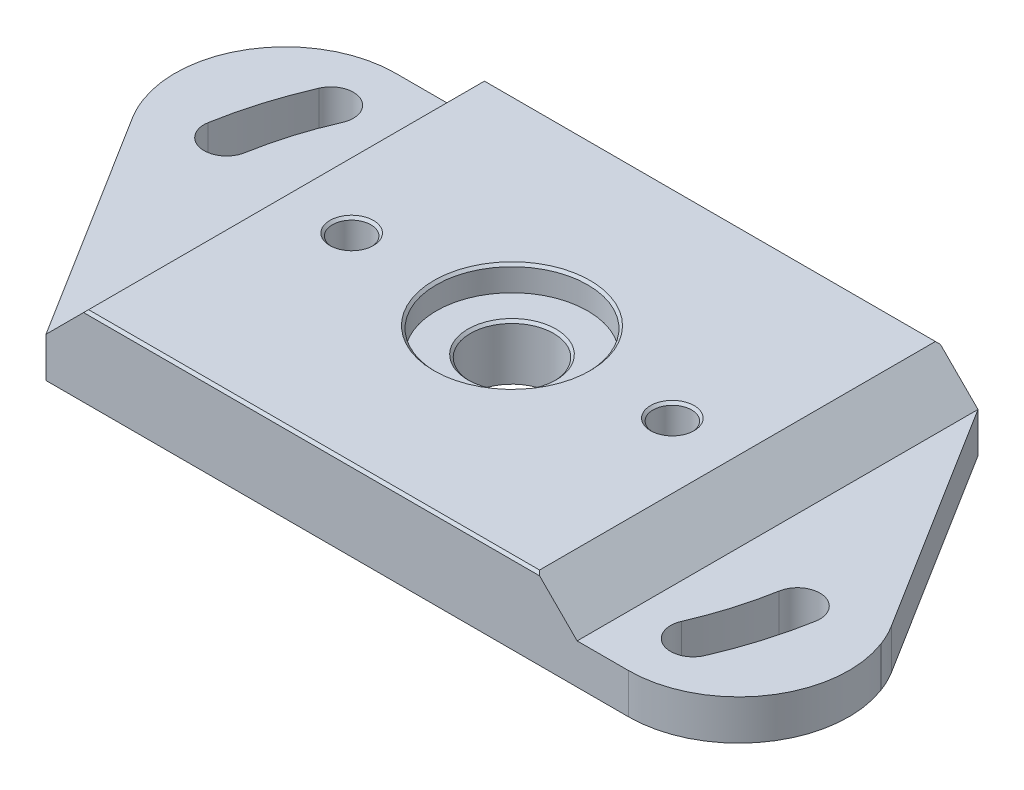
SolidWorks part; units mm, degrees
ref_plane "Front Plane" through (0, 0, 0) normal (0, 0, 1) x (1, 0, 0)
ref_plane "Top Plane" through (0, 0, 0) normal (0, 1, 0) x (1, 0, 0)
ref_plane "Right Plane" through (0, 0, 0) normal (1, 0, 0) x (0, 0, -1)
sketch "Sketch1" plane through (0, 0, 0) normal (0, 1, 0) x (1, 0, 0)
  line L1 (-5, 40) -> (65, 40)
  line L3 (60, 0) -> (0, 0)
  line L4 (-5, 40) -> (-15, 40)
  line L5 (-15, 40) -> (0, 0)
  line L6 (60, 0) -> (80, 0)
  line L7 (80, 0) -> (65, 40)
  point P8 (30, 40)
  point P16 (30, 0)
  dimension "D4" = 70
  dimension "D3" = 10
  dimension "D1" = 60
  dimension "D2" = 40
extrude "Base" add sketch "Sketch1" along normal blind 4
sketch "Sketch2" plane through (0, 4, 0) normal (0, 1, 0) x (1, 0, 0)
  line L0 (65, 40) -> (-15, 40) construction
  line L1 (10, 40) -> (55, 40)
  line L2 (10, 40) -> (10, 0)
  line L3 (10, 0) -> (55, 0)
  line L4 (55, 40) -> (55, 0)
  line L5 (0, 0) -> (80, 0) construction
  dimension "D1" = 10
  dimension "D2" = 10
extrude "TPS Standoff" add sketch "Sketch2" along normal blind 4
sketch "Sketch3" plane through (0, 8, 0) normal (0, 1, 0) x (1, 0, 0)
  line L0 (15, 0) -> (15, 1.5)
  line L1 (10, 40) -> (15, 40)
  line L2 (10, 40) -> (10, 35)
  line L3 (10, 0) -> (15, 0)
  line L4 (55, 40) -> (55, 35)
  line L5 (15, 1.5) -> (11.5, 1.5)
  line L6 (11.5, 1.5) -> (11.5, 5)
  line L7 (11.5, 5) -> (10, 5)
  line L8 (10, 35) -> (11.5, 35)
  line L9 (11.5, 35) -> (11.5, 38.5)
  line L10 (11.5, 38.5) -> (15, 38.5)
  line L11 (15, 38.5) -> (15, 40)
  line L12 (50, 40) -> (50, 38.5)
  line L13 (50, 38.5) -> (53.5, 38.5)
  line L14 (53.5, 38.5) -> (53.5, 35)
  line L15 (53.5, 35) -> (55, 35)
  line L16 (55, 5) -> (53.5, 5)
  line L17 (53.5, 5) -> (53.5, 1.5)
  line L18 (53.5, 1.5) -> (50, 1.5)
  line L19 (50, 1.5) -> (50, 0)
  line L20 (50, 40) -> (55, 40)
  line L21 (55, 5) -> (55, 0)
  line L22 (10, 5) -> (10, 0)
  line L23 (50, 0) -> (55, 0)
  dimension "D1" = 1.5
  dimension "D2" = 5
extrude "TPS Cage" [suppressed] add sketch "Sketch3" along normal blind 1.5
sketch "Sketch4" plane through (0, 8, 0) normal (0, 1, 0) x (1, 0, 0)
  line L0 (10, 40) -> (10, 0) construction
  line L1 (16.5, 20) -> (48.5, 20) construction
  line L2 (10, 0) -> (55, 0) construction
  circle A0 centre (48.5, 20) radius 1.925
  circle A1 centre (16.5, 20) radius 1.925
  point P6 (32.5, 0)
  point P9 (10, 20)
  point P12 (32.5, 20)
  dimension "D2" = 3.85
  dimension "D1" = 32
extrude "TPS Screw Holes" cut sketch "Sketch4" against normal up to surface (8 mm away) up to face at (32.5, 0, -20)
sketch "Sketch5" plane through (0, 4, 0) normal (0, 1, 0) x (1, 0, 0)
  line L0 (-1.9819, 26) -> (-1.9819, 0) construction
  line L1 (0, 0) -> (10, 0) construction
  line L2 (-1.9819, 26) -> (10, 26) construction
  line L4 (66.9819, 40) -> (66.9819, 14) construction
  line L5 (65, 40) -> (55, 40) construction
  line L6 (66.9819, 14) -> (55, 14) construction
  line L8 (-1.9819, 26) -> (66.9819, 14) construction
  line L9 (10, 40) -> (10, 0) construction
  line L10 (55, 0) -> (55, 40) construction
  circle A2 centre (32.5, 20) radius 35 construction
  arc A3 (-1.9819, 26) -> (0.422, 34) centre (32.5, 20) cw construction
  arc A4 (-1.6402, 34.9) -> (-4.1986, 26.3857) centre (32.5, 20) ccw
  arc A5 (2.4841, 33.1) -> (0.2348, 25.6143) centre (32.5, 20) ccw
  arc A6 (2.4841, 33.1) -> (-1.6402, 34.9) centre (0.422, 34) ccw
  arc A7 (-4.1986, 26.3857) -> (0.2348, 25.6143) centre (-1.9819, 26) ccw
  arc A8 (66.9819, 14) -> (64.578, 6) centre (32.5, 20) cw construction
  arc A9 (66.6402, 5.1) -> (69.1986, 13.6143) centre (32.5, 20) ccw
  arc A10 (62.5159, 6.9) -> (64.7652, 14.3857) centre (32.5, 20) ccw
  arc A11 (62.5159, 6.9) -> (66.6402, 5.1) centre (64.578, 6) ccw
  arc A12 (69.1986, 13.6143) -> (64.7652, 14.3857) centre (66.9819, 14) ccw
  point P19 (-1.0195, 30.072)
  point P24 (66.0195, 9.928)
  dimension "D1" = 8
  dimension "D4" = 2.25
  dimension "D2" = 70
  dimension "D3" = 6
extrude "Mounting Screw Holes" cut sketch "Sketch5" against normal up to surface (4 mm away) up to face at (48.5, 0, -21.925)
ref_axis "TPS Shaft Center" through (32.5, 8, -20) along (0, 1, 0)
ref_plane "Shaft Bore Plane" through (32.5, 0, 0) normal (1, 0, 0) x (0, 1, 0)
sketch "Sketch6" plane through (32.5, 0, 0) normal (1, 0, 0) x (0, 1, 0)
  line L0 (8, -20) -> (0, -20)
  line L2 (0, -20) -> (0, -24.15)
  line L3 (0, -24.15) -> (5.5, -24.15)
  line L4 (5.5, -24.15) -> (5.5, -27.55)
  line L5 (5.5, -27.55) -> (8, -27.55)
  line L6 (8, 0) -> (8, -40) construction
  line L7 (8, -27.55) -> (8, -20)
  line L8 (0, 0) -> (0, -40) construction
  point P14 (0, -20)
  dimension "D1" = 7.55
  dimension "D2" = 2.5
  dimension "D3" = 3.4
revolve "TPS Shaft Bore Cut" cut sketch "Sketch6" angle 360 about axis through (32.5, 8, -20) along (0, 1, 0)
sketch "Sketch7" plane through (0, 0, 0) normal (0, -1, 0) x (1, 0, 0)
  circle A0 centre (32.5, -20) radius 7.5
  circle A1 centre (32.5, -20) radius 10
  dimension "D1" = 2.5
  dimension "D2" = 20
extrude "O-Ring Cut" cut sketch "Sketch7" against normal blind 2.5
chamfer "Chamfer1" distance 4 angle 45 2 edges at (55, 4, -20) (10, 4, -20)
fillet "Fillet3" [suppressed] radius 0.5
chamfer "Chamfer2" [suppressed] distance 0.2 angle 45
chamfer "Chamfer3" distance 0.25 angle 45 6 edges at (32.5, 8, 0) (32.5, 8, -40) (32.5, 5.5, -24.15) (48.5, 8, -18.075) (16.5, 8, -18.075) (32.5, 8, -27.55)
sketch "Sketch9" plane through (0, 4, 0) normal (0, 1, 0) x (1, 0, 0)
  line L0 (6, 0) -> (-9, 24)
  line L1 (-15, 40) -> (0, 0) construction
  line L2 (-9, 24) -> (0, 0)
  line L3 (0, 0) -> (6, 0)
  line L4 (59, 40) -> (65, 40)
  line L5 (65, 40) -> (74, 16)
  line L6 (80, 0) -> (65, 40) construction
  line L7 (74, 16) -> (59, 40)
  line L8 (59, 40) -> (59, 0) construction
  dimension "D1" = 24
extrude "Cut-Extrude3" cut sketch "Sketch9" against normal through all both
fillet "Fillet4" radius 11 4 edges at (-15, 2, -40) (80, 2, 0) (74, 2, -16) (-9, 2, -24)
